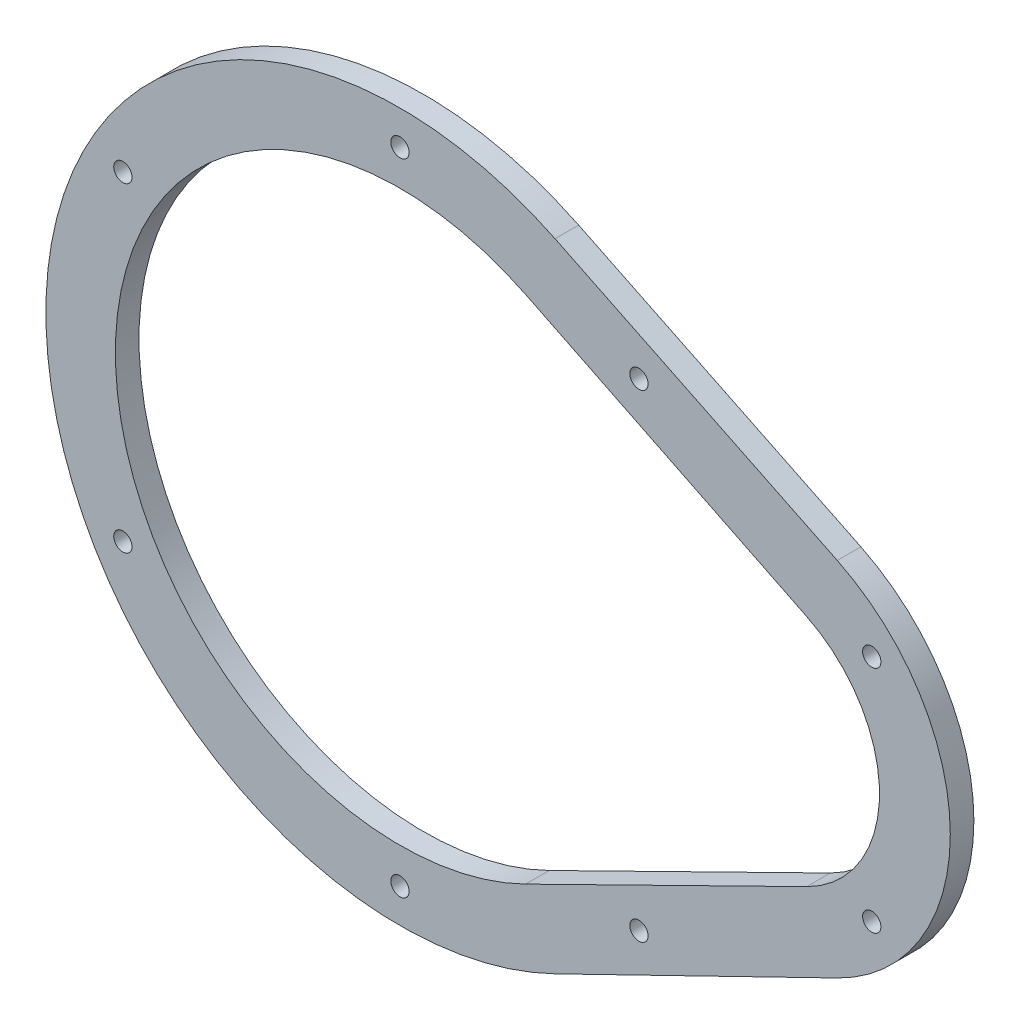
SolidWorks part; units mm, degrees
ref_plane "Front Plane" through (0, 0, 0) normal (0, 0, 1) x (1, 0, 0)
ref_plane "Top Plane" through (0, 0, 0) normal (0, 1, 0) x (1, 0, 0)
ref_plane "Right Plane" through (0, 0, 0) normal (1, 0, 0) x (0, 0, -1)
sketch "Sketch1" plane through (0, 0, 0) normal (0, 0, 1) x (1, 0, 0)
  line L0 (26.281, 53.938) -> (74.1028, 30.6371)
  line L1 (0, 0) -> (59.175, 0) construction
  line L3 (26.281, -53.938) -> (74.1028, -30.6371)
  line L4 (23.9475, 48.6458) -> (71.5904, 25.22) construction
  line L5 (23.9475, -48.6458) -> (72.6458, -24.6724) construction
  line L6 (21.2975, 43.2627) -> (68.9293, 19.8144)
  line L7 (21.2975, -43.2627) -> (68.9293, -19.8144)
  circle A1 centre (0, 0) radius 60 construction
  circle A11 centre (59.175, 0) radius 34.0804 construction
  arc A12 (26.281, 53.938) -> (26.281, -53.938) centre (0, 0) ccw
  arc A13 (74.1028, 30.6371) -> (74.1028, -30.6371) centre (59.175, 0) cw
  circle A16 centre (0, 0) radius 48.2208 construction
  circle A17 centre (59.175, 0) radius 22.0852 construction
  arc A18 (23.9475, 48.6458) -> (23.9475, -48.6458) centre (0, 0) ccw construction
  arc A19 (71.5904, 25.22) -> (72.6458, -24.6724) centre (59.175, 0) cw construction
  arc A20 (21.2975, 43.2627) -> (21.2975, -43.2627) centre (0, 0) ccw
  arc A21 (68.9293, 19.8144) -> (68.9293, -19.8144) centre (59.175, 0) cw
  point P22 (0, 0)
extrude "Boss-Extrude2" add sketch "Sketch1" along normal blind 4
sketch "Sketch11" plane through (0, 0, 4) normal (0, 0, 1) x (1, 0, 0)
  line L0 (0, 0) -> (60.5, 0) construction
  line L1 (23.9475, 48.6458) -> (72.6458, 24.6724) construction
  line L2 (23.9475, -48.6458) -> (72.6458, -24.6724) construction
  line L4 (0, 0) -> (40.4982, 40.4982) construction
  line L5 (60.5, 0) -> (79.9454, 19.4454) construction
  circle A15 centre (60.5, 0) radius 27.5 construction
  circle A16 centre (0, 0) radius 54.2208 construction
  circle A17 centre (0, 54.2208) radius 1.55
  circle A18 centre (-46.9566, 27.1104) radius 1.55
  circle A19 centre (-46.9566, -27.1104) radius 1.55
  circle A20 centre (0, -54.2208) radius 1.55
  circle A21 centre (79.9454, 19.4454) radius 1.55
  circle A23 centre (40.4982, 40.4982) radius 1.55
  circle A24 centre (79.9454, -19.4454) radius 1.55
  circle A25 centre (40.4982, -40.4982) radius 1.55
  point P22 (0, 0)
  point P45 (0, 0)
  point P47 (60.5, 0)
extrude "Cut-Extrude4" cut sketch "Sketch11" along normal offset from surface 10 and the other way through all up to face at (33.4098, 0, 0)
